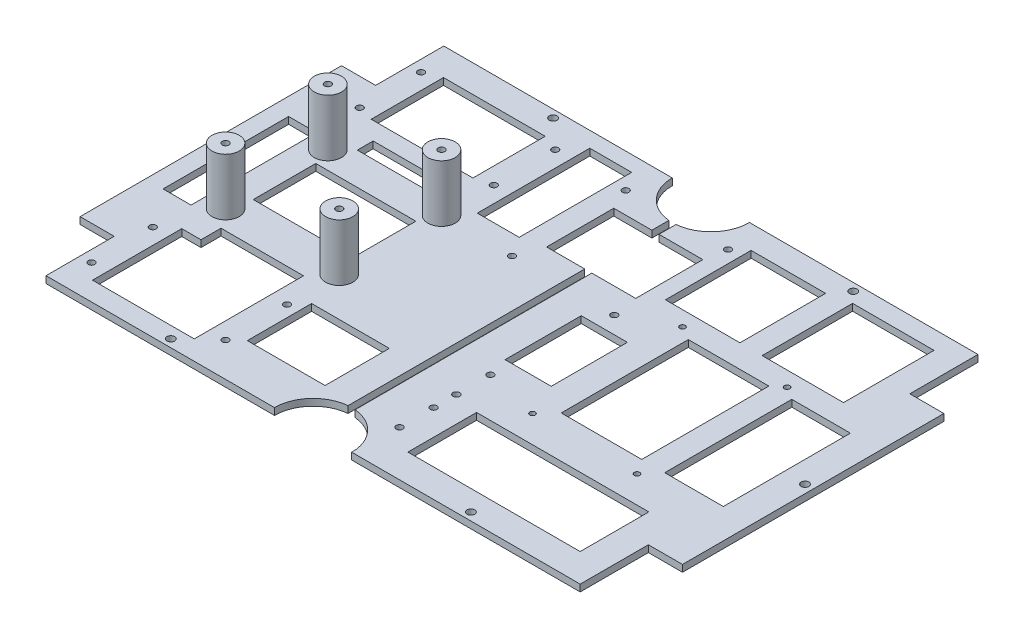
SolidWorks part; units mm, degrees
ref_plane "Płaszczyzna przednia" through (0, 0, 0) normal (0, 0, 1) x (1, 0, 0)
ref_plane "Płaszczyzna górna" through (0, 0, 0) normal (0, 1, 0) x (1, 0, 0)
ref_plane "Płaszczyzna prawa" through (0, 0, 0) normal (1, 0, 0) x (0, 0, -1)
sketch "Sketch1" plane through (0, 0, 0) normal (0, 1, 0) x (1, 0, 0)
  line L16 (-132.5, 87.5) -> (132.5, 87.5)
  line L18 (-132.5, 87.5) -> (-132.5, -87.5)
  line L19 (-132.5, -87.5) -> (132.5, -87.5)
  line L20 (132.5, 87.5) -> (132.5, -87.5)
  line L21 (-132.5, 87.5) -> (132.5, -87.5) construction
  line L22 (-132.5, -87.5) -> (132.5, 87.5) construction
  point P0 (0, 0)
  dimension "D2" = 175
  dimension "D1" = 265
extrude "Boss-Extrude3" add sketch "Sketch1" along normal blind 3
sketch "Sketch2" plane through (0, 3, 0) normal (0, 1, 0) x (1, 0, 0)
  line L0 (132.5, 0) -> (65, 0) construction
  line L1 (132.5, -87.5) -> (132.5, 87.5) construction
  line L2 (-53.5, -45.5) -> (-53.5, 45.5) construction
  line L3 (42, -33) -> (88, -33) construction
  line L4 (42, -33) -> (42, 33) construction
  line L5 (42, 33) -> (88, 33) construction
  line L6 (88, -33) -> (88, 33) construction
  line L7 (42, -33) -> (88, 33) construction
  line L8 (42, 33) -> (88, -33) construction
  line L10 (-132.5, -87.5) -> (-112.5, -87.5) construction
  line L11 (-132.5, -87.5) -> (-132.5, -72.5) construction
  line L12 (-132.5, -72.5) -> (-112.5, -72.5) construction
  line L13 (-112.5, -87.5) -> (-112.5, -72.5) construction
  line L14 (-112.5, -72.5) -> (-53.5, -72.5) construction
  line L15 (-112.5, -72.5) -> (-112.5, -45.5) construction
  line L16 (-112.5, -45.5) -> (-53.5, -45.5) construction
  line L17 (-53.5, -72.5) -> (-53.5, -45.5) construction
  line L18 (-53.5, 45.5) -> (-112.5, 45.5) construction
  line L19 (-53.5, 45.5) -> (-53.5, 72.5) construction
  line L20 (-53.5, 72.5) -> (-112.5, 72.5) construction
  line L21 (-112.5, 45.5) -> (-112.5, 72.5) construction
  line L22 (-53.5, -22.5) -> (-103.5, -22.5) construction
  line L23 (0, 87.5) -> (0, 72.5) construction
  line L28 (132.5, 87.5) -> (-132.5, 87.5) construction
  line L29 (0, 72.5) -> (22.5, 72.5) construction
  line L30 (22.5, 72.5) -> (22.5, 22.5) construction
  line L31 (22.5, 22.5) -> (-22.5, 22.5) construction
  line L32 (-22.5, 22.5) -> (-22.5, 72.5) construction
  line L33 (-22.5, 72.5) -> (0, 72.5) construction
  line L34 (0, -87.5) -> (0, -67.5) construction
  line L35 (-132.5, -87.5) -> (132.5, -87.5) construction
  line L36 (0, -67.5) -> (18, -67.5) construction
  line L37 (18, -67.5) -> (18, -52.5) construction
  line L38 (18, -52.5) -> (18, -42.5) construction
  line L39 (18, -42.5) -> (18, -27.5) construction
  line L40 (-53.5, -22.5) -> (-53.5, 22.5) construction
  line L45 (-53.5, 22.5) -> (-103.5, 22.5) construction
  line L46 (-103.5, -22.5) -> (-103.5, 22.5) construction
  circle A0 centre (88, 33) radius 1.2
  circle A1 centre (42, 33) radius 1.2
  circle A2 centre (88, -33) radius 1.2
  circle A3 centre (42, -33) radius 1.2
  circle A4 centre (18, -67.5) radius 1.45
  circle A5 centre (18, -52.5) radius 1.45
  circle A6 centre (18, -42.5) radius 1.45
  circle A7 centre (18, -27.5) radius 1.45
  circle A8 centre (-53.5, -72.5) radius 1.45
  circle A9 centre (-53.5, -45.5) radius 1.45
  circle A10 centre (-112.5, -45.5) radius 1.45
  circle A11 centre (-112.5, -72.5) radius 1.45
  circle A12 centre (-112.5, 45.5) radius 1.45
  circle A13 centre (-53.5, 45.5) radius 1.45
  circle A14 centre (-53.5, 72.5) radius 1.45
  circle A15 centre (-112.5, 72.5) radius 1.45
  circle A20 centre (-22.5, 22.5) radius 1.45
  circle A21 centre (22.5, 22.5) radius 1.45
  circle A22 centre (-22.5, 72.5) radius 1.45
  circle A23 centre (22.5, 72.5) radius 1.45
  dimension "D3" = 20
  dimension "D11" = 45
  dimension "D1" = 66
  dimension "D2" = 46
  dimension "D4" = 15
  dimension "D5" = 27
  dimension "D6" = 59
  dimension "D7" = 27
  dimension "D8" = 59
  dimension "D9" = 15
  dimension "D10" = 50
  dimension "D12" = 23
  dimension "D13" = 23
extrude "Cut-Extrude1" cut sketch "Sketch2" against normal blind 10
sketch "Sketch3" plane through (0, 3, 0) normal (0, 1, 0) x (1, 0, 0)
  line L0 (132.5, 0) -> (128.9, 0) construction
  line L1 (132.5, -87.5) -> (132.5, 87.5) construction
  line L2 (-132.5, 0) -> (-128.9, 0) construction
  line L3 (-132.5, 87.5) -> (-132.5, -87.5) construction
  line L4 (-128.9, 0) -> (-66, 0) construction
  line L5 (-66, 0) -> (-66, 84.1) construction
  line L6 (-66, 0) -> (-66, -84.1) construction
  line L7 (-66, 84.1) -> (66, 84.1) construction
  line L8 (-66, -84.1) -> (66, -84.1) construction
  circle A0 centre (-66, 84.1) radius 1.7
  circle A1 centre (-128.9, 0) radius 1.7
  circle A2 centre (-66, -84.1) radius 1.7
  circle A3 centre (66, -84.1) radius 1.7
  circle A4 centre (66, 84.1) radius 1.7
  circle A5 centre (128.9, 0) radius 1.7
extrude "Cut-Extrude2" cut sketch "Sketch3" against normal blind 10
sketch "Sketch4" plane through (0, 3, 0) normal (0, 1, 0) x (1, 0, 0)
  line L0 (132.5, 87.5) -> (-132.5, 87.5) construction
  line L1 (-132.5, -87.5) -> (132.5, -87.5) construction
  line L3 (-132.5, 87.5) -> (-117.5, 87.5)
  line L4 (-132.5, 87.5) -> (-132.5, 57.5)
  line L5 (-132.5, 57.5) -> (-117.5, 57.5)
  line L6 (-117.5, 87.5) -> (-117.5, 57.5)
  line L7 (-132.5, -87.5) -> (-117.5, -87.5)
  line L8 (-132.5, -87.5) -> (-132.5, -57.5)
  line L9 (-132.5, -57.5) -> (-117.5, -57.5)
  line L10 (-117.5, -87.5) -> (-117.5, -57.5)
  line L11 (132.5, -87.5) -> (117.5, -87.5)
  line L12 (132.5, -87.5) -> (132.5, -57.5)
  line L13 (132.5, -57.5) -> (117.5, -57.5)
  line L14 (117.5, -87.5) -> (117.5, -57.5)
  line L15 (132.5, 87.5) -> (117.5, 87.5)
  line L16 (132.5, 87.5) -> (132.5, 57.5)
  line L17 (132.5, 57.5) -> (117.5, 57.5)
  line L18 (117.5, 87.5) -> (117.5, 57.5)
  circle A0 centre (0, 87.5) radius 17
  circle A1 centre (0, -87.5) radius 17
  dimension "D1" = 30
  dimension "D2" = 15
  dimension "D3" = 30
  dimension "D4" = 15
extrude "Cut-Extrude3" cut sketch "Sketch4" against normal blind 10
sketch "Sketch5" plane through (0, 3, 0) normal (0, 1, 0) x (1, 0, 0)
  circle A0 centre (-53.5, 22.5) radius 6
  circle A1 centre (-53.5, -22.5) radius 6
  circle A2 centre (-103.5, -22.5) radius 6
  circle A3 centre (-103.5, 22.5) radius 6
  point P14 (-100.7536, 24.2684)
  dimension "D1" = 45
  dimension "D2" = 50
  dimension "D3" = 50
  dimension "D4" = 45
extrude "Boss-Extrude4" add sketch "Sketch5" along normal blind 25
sketch "Sketch6" plane through (0, 28, 0) normal (0, 1, 0) x (1, 0, 0)
  circle A0 centre (-103.5, 22.5) radius 1.45
  circle A1 centre (-53.5, 22.5) radius 1.45
  circle A2 centre (-53.5, -22.5) radius 1.45
  circle A3 centre (-103.5, -22.5) radius 1.45
extrude "Cut-Extrude4" cut sketch "Sketch6" against normal blind 16
sketch "Sketch7" plane through (0, 3, 0) normal (0, 1, 0) x (1, 0, 0)
  line L1 (-1.5668, -70.5724) -> (1.5668, -70.5724)
  line L2 (-1.5668, -70.5724) -> (-1.5668, 70.5724)
  line L3 (-1.5668, 70.5724) -> (1.5668, 70.5724)
  line L4 (1.5668, -70.5724) -> (1.5668, 70.5724)
  line L5 (-1.5668, -70.5724) -> (1.5668, 70.5724) construction
  line L6 (-1.5668, 70.5724) -> (1.5668, -70.5724) construction
  arc A0 (-17, 87.5) -> (17, 87.5) centre (0, 87.5) ccw construction
  point P0 (0, 0)
extrude "Cut-Extrude5" cut sketch "Sketch7" against normal blind 16
sketch "Sketch8" plane through (0, 3, 0) normal (0, 1, 0) x (1, 0, 0)
  line L1 (-100.9203, -12.8956) -> (-56.9163, -12.8956)
  line L2 (-100.9203, -12.8956) -> (-100.9203, 14.6069)
  line L3 (-100.9203, 14.6069) -> (-56.9163, 14.6069)
  line L4 (-56.9163, -12.8956) -> (-56.9163, 14.6069)
  line L5 (-112.5004, -28.6939) -> (-124.8041, -28.6939)
  line L6 (-112.5004, -28.6939) -> (-112.5004, 26.5182)
  line L7 (-112.5004, 26.5182) -> (-124.8041, 26.5182)
  line L8 (-124.8041, -28.6939) -> (-124.8041, 26.5182)
  line L9 (-105.568, 43.6252) -> (-60.8155, 43.6252)
  line L10 (-105.568, 43.6252) -> (-105.568, 75.4196)
  line L11 (-105.568, 75.4196) -> (-60.8155, 75.4196)
  line L12 (-60.8155, 43.6252) -> (-60.8155, 75.4196)
  line L21 (-46.4644, 80.6781) -> (-28.0466, 80.6781)
  line L22 (-46.4644, 80.6781) -> (-46.4644, 31.1977)
  line L23 (-46.4644, 31.1977) -> (-28.0466, 31.1977)
  line L24 (-28.0466, 80.6781) -> (-28.0466, 31.1977)
  line L25 (-96.8686, 28.8192) -> (-61.2463, 28.8192)
  line L26 (-96.8686, 28.8192) -> (-96.8686, 35.7775)
  line L27 (-96.8686, 35.7775) -> (-61.2463, 35.7775)
  line L28 (-61.2463, 28.8192) -> (-61.2463, 35.7775)
  line L29 (-105.568, -78.974) -> (-60.8155, -78.974)
  line L30 (-105.568, -78.974) -> (-105.568, -39.7113)
  line L31 (-105.568, -39.7113) -> (-60.8155, -39.7113)
  line L32 (-60.8155, -78.974) -> (-60.8155, -39.7113)
  line L33 (-60.8155, -39.7113) -> (-97.1012, -39.7113)
  line L34 (-60.8155, -39.7113) -> (-60.8155, -30.8994)
  line L35 (-60.8155, -30.8994) -> (-97.1012, -30.8994)
  line L36 (-97.1012, -39.7113) -> (-97.1012, -30.8994)
  line L37 (-48.4867, -67.9542) -> (-14.283, -67.9542)
  line L38 (-48.4867, -67.9542) -> (-48.4867, -39.6743)
  line L39 (-48.4867, -39.6743) -> (-14.283, -39.6743)
  line L40 (-14.283, -67.9542) -> (-14.283, -39.6743)
  line L42 (-18.3295, 33.5586) -> (20.8655, 33.5586)
  line L43 (-18.3295, 33.5586) -> (-18.3295, 63.0967)
  line L44 (-18.3295, 63.0967) -> (20.8655, 63.0967)
  line L45 (20.8655, 33.5586) -> (20.8655, 63.0967)
  line L46 (27.9519, 39.5751) -> (60.6973, 39.5751)
  line L47 (27.9519, 39.5751) -> (27.9519, 77.2415)
  line L48 (27.9519, 77.2415) -> (60.6973, 77.2415)
  line L49 (60.6973, 39.5751) -> (60.6973, 77.2415)
  line L50 (70.4634, 39.5751) -> (106.2727, 39.5751)
  line L51 (70.4634, 39.5751) -> (70.4634, 79.3709)
  line L52 (70.4634, 79.3709) -> (106.2727, 79.3709)
  line L53 (106.2727, 39.5751) -> (106.2727, 79.3709)
  line L54 (48.1174, -26.46) -> (83.5385, -26.46)
  line L55 (48.1174, -26.46) -> (48.1174, 29.4455)
  line L56 (48.1174, 29.4455) -> (83.5385, 29.4455)
  line L57 (83.5385, -26.46) -> (83.5385, 29.4455)
  line L58 (35.7695, -18.51) -> (15.4663, -18.51)
  line L59 (35.7695, -18.51) -> (35.7695, 14.991)
  line L60 (35.7695, 14.991) -> (15.4663, 14.991)
  line L61 (15.4663, -18.51) -> (15.4663, 14.991)
  line L62 (29.296, -75.102) -> (105.0854, -75.102)
  line L63 (29.296, -75.102) -> (29.296, -44.891)
  line L64 (29.296, -44.891) -> (105.0854, -44.891)
  line L65 (105.0854, -75.102) -> (105.0854, -44.891)
  line L66 (93.643, -26.46) -> (119.4209, -26.46)
  line L67 (93.643, -26.46) -> (93.643, 29.4455)
  line L68 (93.643, 29.4455) -> (119.4209, 29.4455)
  line L69 (119.4209, -26.46) -> (119.4209, 29.4455)
  point P12 (-1.5668, -75.102)
  point P13 (-1.5668, -70.5724)
  point P14 (-47.095, 34.3997)
  point P15 (-26.404, 32.2129)
  point P16 (-18.3295, 33.5586)
  point P17 (35.7695, -18.51)
  point P18 (-95.933, -35.4888)
  point P19 (-60.7401, -39.7113)
  point P32 (-46.4644, 31.1977)
  line M21 (-1.5668, -70.5724) -> (-1.5668, 70.5724)
extrude "Cut-Extrude6" cut sketch "Sketch8" against normal blind 10 contours L9 L12 L11 L10 | L8 L5 L6 L7 | L1 L4 L3 L2 | L29 L32 L31 L30 | L36 L31 L34 L35 | L25 L28 L27 L26 | L24 L21 L22 L23 | L37 L40 L39 L38 | L44 L43 L42 M21 | L42 L45 L44 M21 | L46 L49 L48 L47 | L50 L53 L52 L51 | L54 L57 L56 L55 | L66 L69 L68 L67 | L62 L65 L64 L63 | L61 L58 L59 L60 region at (-78.9183, 3, -0.8557) region at (-118.6522, 3, 1.0878) region at (-83.1917, 3, -59.5224) region at (-37.2555, 3, -55.9379) region at (-79.0574, 3, -32.2983) region at (-83.1917, 3, 59.3427) region at (-78.9584, 3, 35.3054) region at (-31.3848, 3, 53.8142) region at (-9.9482, 3, -48.3276) region at (9.6493, 3, -48.3276) region at (44.3246, 3, -58.4083) region at (88.3681, 3, -59.473) region at (65.8279, 3, -1.4928) region at (25.6179, 3, 1.7595) region at (67.1907, 3, 59.9965) region at (106.5319, 3, -1.4928)
